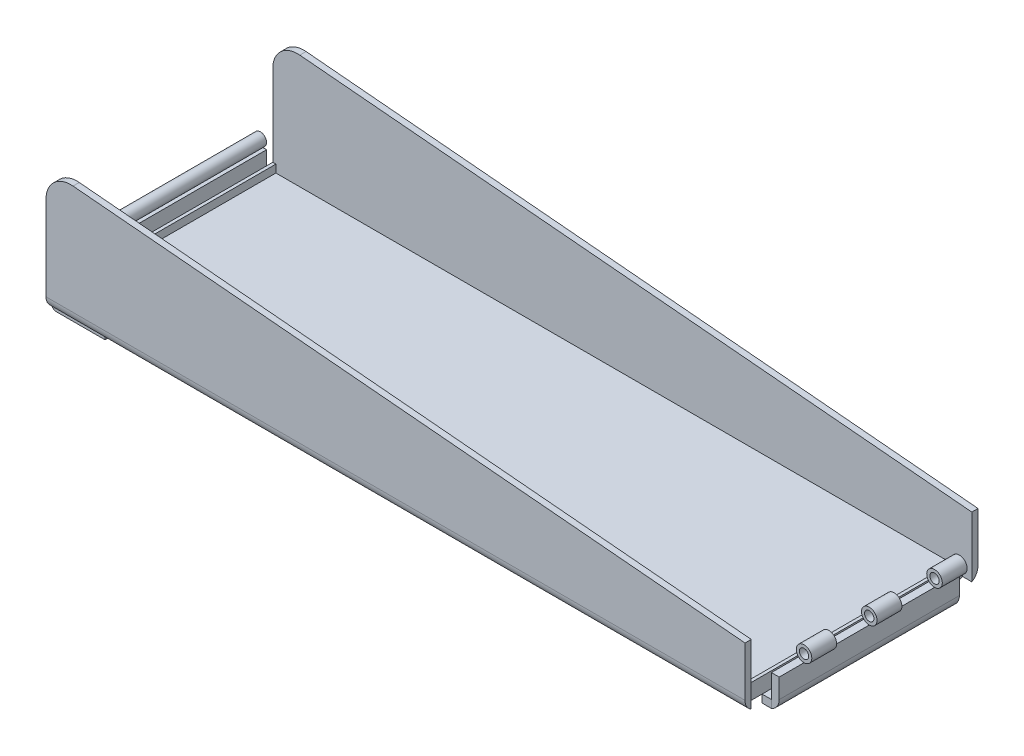
SolidWorks part; units mm, degrees
material "1060 Alloy"
ref_plane "Front Plane" through (0, 0, 0) normal (0, 0, 1) x (1, 0, 0)
ref_plane "Top Plane" through (0, 0, 0) normal (0, 1, 0) x (1, 0, 0)
ref_plane "Right Plane" through (0, 0, 0) normal (1, 0, 0) x (0, 0, -1)
sketch "Sketch1" plane through (0, 0, 0) normal (0, 1, 0) x (1, 0, 0)
  line L1 (-140.97, 47.625) -> (140.97, 47.625)
  line L2 (-140.97, 47.625) -> (-140.97, -47.625)
  line L3 (-140.97, -47.625) -> (140.97, -47.625)
  line L4 (140.97, 47.625) -> (140.97, -47.625)
  line L5 (-140.97, 47.625) -> (140.97, -47.625) construction
  line L6 (-140.97, -47.625) -> (140.97, 47.625) construction
  point P0 (0, 0)
  dimension "D1" = 281.94
  dimension "D2" = 95.25
extrude "Boss-Extrude1" add sketch "Sketch1" along normal blind 3.175
ref_plane "Plane1" through (140.97, 0, 0) normal (1, 0, 0) x (0, 0, -1)
sketch "Sketch2" plane through (140.97, 0, 0) normal (1, 0, 0) x (0, 0, -1)
  line L0 (47.625, 3.175) -> (47.625, 0) construction
  line L1 (-47.625, 3.175) -> (47.625, 3.175)
  line L2 (-47.625, 3.175) -> (-47.625, 6.35)
  line L3 (-47.625, 6.35) -> (47.625, 6.35)
  line L4 (47.625, 3.175) -> (47.625, 6.35)
  dimension "D1" = 3.175
extrude "Boss-Extrude2" add sketch "Sketch2" against normal blind 1.27
ref_plane "Plane2" through (0, 0, 47.625) normal (0, 0, 1) x (1, 0, 0)
sketch "Sketch4" plane through (0, 0, 47.625) normal (0, 0, 1) x (1, 0, 0)
  line L0 (-140.97, 3.175) -> (-140.97, 0) construction
  line L1 (144.78, 0) -> (-140.97, 0)
  line L2 (144.78, 0) -> (144.78, 25.4)
  line L4 (-140.97, 0) -> (-140.97, 50.8)
  line L5 (-140.97, 50.8) -> (144.78, 25.4)
  dimension "D1" = 50.8
  dimension "D2" = 25.4
  dimension "D3" = 285.75
extrude "Boss-Extrude3" add sketch "Sketch4" against normal blind 2.54
mirror "Mirror1" about plane through (0, 0, 0) normal (0, 0, 1) of "Boss-Extrude3"
mirror "Mirror2" about plane through (0, 0, 0) normal (1, 0, 0) of "Boss-Extrude2"
fillet "Fillet2" radius 10.16 1 edges at (-140.97, 50.8, 46.355)
fillet "Fillet3" radius 10.16 1 edges at (-140.97, 50.8, -46.355)
fillet "Fillet4" radius 5.08 1 edges at (1.905, 0, 47.625)
fillet "Fillet5" radius 5.08 1 edges at (1.905, 0, -47.625)
sketch "Sketch12" plane through (0, 0, 0) normal (0, -1, 0) x (1, 0, 0)
  line L1 (140.97, -36.83) -> (144.78, -36.83)
  line L2 (140.97, -36.83) -> (140.97, 36.83)
  line L3 (140.97, 36.83) -> (144.78, 36.83)
  line L4 (144.78, -36.83) -> (144.78, 36.83)
  line L5 (140.97, -45.085) -> (140.97, 45.085) construction
  line L6 (144.78, 45.085) -> (144.78, 47.625) construction
  point P6 (140.97, 0)
  dimension "D1" = 73.66
extrude "Boss-Extrude8" add sketch "Sketch12" along normal blind 3.175
sketch "Sketch13" plane through (144.78, 0, 0) normal (1, 0, 0) x (0, 0, -1)
  line L0 (-36.83, -3.175) -> (-36.83, 0) construction
  line L1 (36.83, -3.175) -> (-36.83, -3.175)
  line L2 (36.83, -3.175) -> (36.83, 9.525)
  line L3 (36.83, 9.525) -> (-36.83, 9.525)
  line L4 (-36.83, -3.175) -> (-36.83, 9.525)
  dimension "D1" = 12.7
extrude "Boss-Extrude9" add sketch "Sketch13" along normal blind 3.175
fillet "Fillet7" radius 5.08 1 edges at (147.955, -3.175, 0)
sketch "Sketch14" plane through (0, 0, -36.83) normal (0, 0, -1) x (-1, 0, 0)
  line L0 (-147.955, 1.5343) -> (-147.955, 9.525) construction
  line L1 (-147.955, 9.525) -> (-144.78, 9.525) construction
  circle A0 centre (-147.955, 12.7) radius 3.175
  dimension "D1" = 6.35
extrude "Boss-Extrude11" add sketch "Sketch14" against normal blind 10.16 separate body
pattern_linear "LPattern1" count 3 spacing 26.67 along (0, 0, 1) of "Boss-Extrude11"
sketch "Sketch15" plane through (0, 0, -36.83) normal (0, 0, -1) x (-1, 0, 0)
  circle A0 centre (-147.955, 12.7) radius 1.905
  dimension "D1" = 3.81
extrude "Cut-Extrude1" cut sketch "Sketch15" against normal through all both and the other way through all
sketch "Sketch16" plane through (0, 0, 0) normal (0, -1, 0) x (1, 0, 0)
  line L0 (140.97, 42.545) -> (-140.97, 42.545) construction
  line L1 (-121.92, 42.545) -> (-140.97, 42.545)
  line L2 (-121.92, 42.545) -> (-121.92, -42.545)
  line L3 (-121.92, -42.545) -> (-140.97, -42.545)
  line L4 (-140.97, 42.545) -> (-140.97, -42.545)
  dimension "D1" = 19.05
extrude "Boss-Extrude12" add sketch "Sketch16" along normal blind 3.175
sketch "Sketch17" plane through (-140.97, 0, 0) normal (-1, 0, 0) x (0, 0, 1)
  line L1 (42.545, -3.175) -> (-42.545, -3.175)
  line L2 (42.545, -3.175) -> (42.545, 12.065)
  line L3 (42.545, 12.065) -> (-42.545, 12.065)
  line L4 (-42.545, -3.175) -> (-42.545, 12.065)
  dimension "D1" = 15.24
extrude "Boss-Extrude13" add sketch "Sketch17" along normal blind 3.175 contours L2 L1 L4 L3
sketch "Sketch18" plane through (0, 0, -42.545) normal (0, 0, -1) x (-1, 0, 0)
  line L0 (140.97, 39.6968) -> (140.97, 5.08) construction
  line L1 (144.145, 12.065) -> (140.97, 12.065) construction
  circle A0 centre (143.51, 14.605) radius 2.54
  circle A1 centre (143.51, 14.605) radius 1.905
  dimension "D1" = 5.08
  dimension "D2" = 3.81
extrude "Boss-Extrude14" add sketch "Sketch18" against normal up to surface (85.09 mm away) separate body contours A0 up to face at (-136.4343, 3.4471, 42.545)
sketch "Sketch20" plane through (0, 0, -42.545) normal (0, 0, -1) x (-1, 0, 0)
  circle A0 centre (143.51, 14.605) radius 1.905
  dimension "D1" = 3.81
extrude "Cut-Extrude7" cut sketch "Sketch20" against normal through all both and the other way through all
fillet "Fillet8" radius 2.54 1 edges at (-144.145, -3.175, 0)
